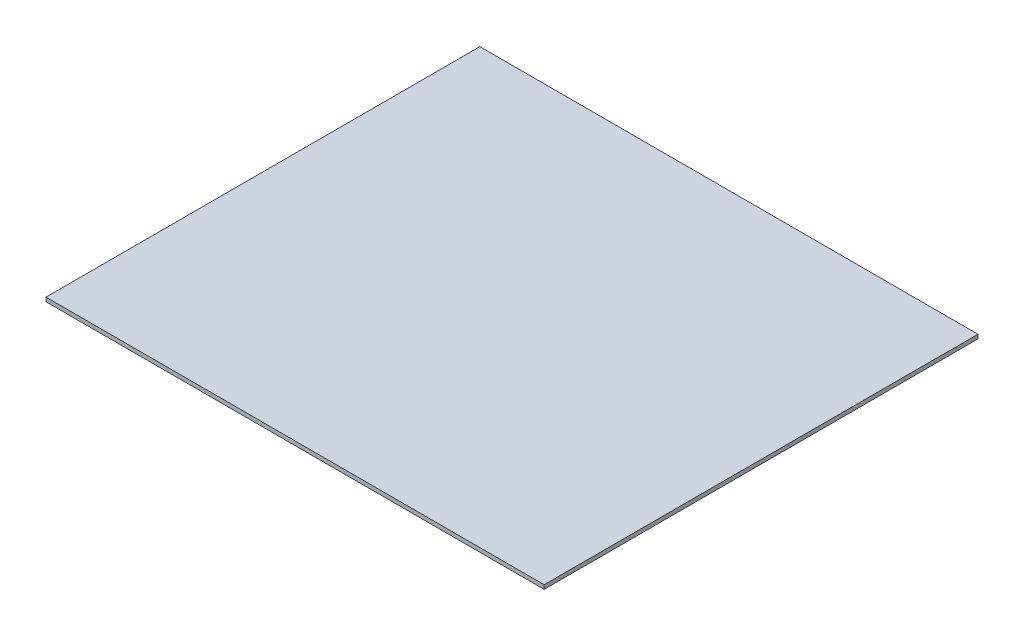
SolidWorks part; units mm, degrees
material "Acrylic (Medium-high impact)"
ref_plane "Front Plane" through (0, 0, 0) normal (0, 0, 1) x (1, 0, 0)
ref_plane "Top Plane" through (0, 0, 0) normal (0, 1, 0) x (1, 0, 0)
ref_plane "Right Plane" through (0, 0, 0) normal (1, 0, 0) x (0, 0, -1)
sketch "Sketch1" plane through (0, 0, 0) normal (0, 1, 0) x (1, 0, 0)
  line L1 (-196.85, -171.45) -> (196.85, -171.45)
  line L2 (-196.85, -171.45) -> (-196.85, 171.45)
  line L3 (-196.85, 171.45) -> (196.85, 171.45)
  line L4 (196.85, -171.45) -> (196.85, 171.45)
  line L5 (-196.85, -171.45) -> (196.85, 171.45) construction
  line L6 (-196.85, 171.45) -> (196.85, -171.45) construction
  point P0 (0, 0)
  dimension "D1" = 342.9
  dimension "D2" = 393.7
extrude "Boss-Extrude1" add sketch "Sketch1" along normal blind 3.175
